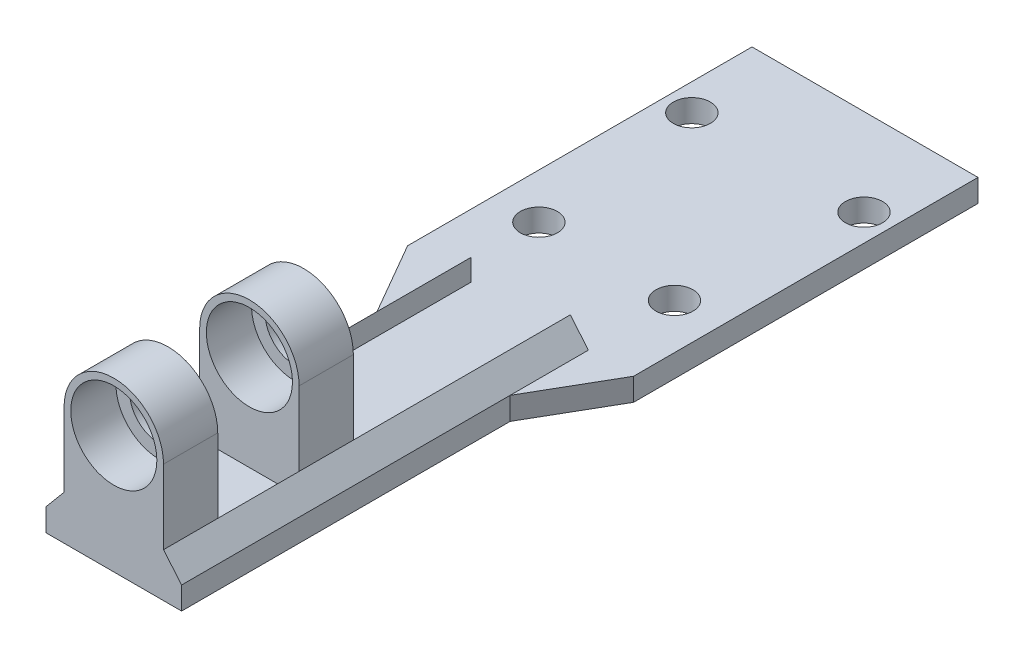
SolidWorks part; units mm, degrees
ref_plane "Plan de face" through (0, 0, 0) normal (0, 0, 1) x (1, 0, 0)
ref_plane "Plan de dessus" through (0, 0, 0) normal (0, 1, 0) x (1, 0, 0)
ref_plane "Plan de droite" through (0, 0, 0) normal (1, 0, 0) x (0, 0, -1)
sketch "Esquisse20" plane through (0, 0, 0) normal (0, -1, 0) x (1, 0, 0)
  line L0 (-25, 0) -> (-15, 17.3205)
  line L1 (-15, 17.3205) -> (-15, 90)
  line L2 (-15, 90) -> (15, 90)
  line L3 (15, 90) -> (15, 17.3205)
  line L4 (15, 17.3205) -> (25, 0)
  line L5 (0, 25.5) -> (0, 57.1166) construction
  line L6 (55, 0) -> (-55, 0) construction
  line L7 (0, -55) -> (0, 55) construction
  line L10 (-25, 0) -> (25, 0)
  dimension "D1" = 90
  dimension "D2" = 60
  dimension "D3" = 30
  dimension "D4" = 50
extrude "Boss.-Extru.7" add sketch "Esquisse20" against normal blind 5
sketch "Esquisse21" plane through (0, 0, 90) normal (0, 0, 1) x (1, 0, 0)
  line L0 (-15, 5) -> (-11, 9.767)
  line L1 (-11, 9.767) -> (-11, 26.15)
  line L2 (15, 5) -> (-15, 5)
  line L3 (11, 26.15) -> (11, 9.767)
  line L4 (11, 9.767) -> (15, 5)
  line L5 (0, 0) -> (0, 46.5044) construction
  line L7 (15, 5) -> (-15, 5) construction
  arc A0 (11, 26.15) -> (-11, 26.15) centre (0, 26.15) ccw
  point P11 (0, 5)
  dimension "D2" = 11
  dimension "D1" = 21.15
  dimension "D3" = 50
extrude "Boss.-Extru.8" add sketch "Esquisse21" against normal blind 12
ref_axis "Axe1" through (0, 5, 78) along (0, 0, -1)
sketch "Esquisse25" plane through (0, 0, 90) normal (0, 0, 1) x (1, 0, 0)
  circle A0 centre (0, 26.15) radius 9.525
  dimension "D1" = 19.05
extrude "Enlèv. mat.-Extru.1" cut sketch "Esquisse25" against normal blind 10
pattern_linear "Répétition linéaire2" count 2 spacing 30 along (0, 0, -1) of "Boss.-Extru.8", "Enlèv. mat.-Extru.1"
sketch "Esquisse22" plane through (0, 5, 0) normal (0, 1, 0) x (1, 0, 0)
  line L0 (-25, 0) -> (25, 0) construction
  line L1 (-25, 0) -> (25, 0)
  line L2 (-25, 0) -> (-25, 38.1)
  line L3 (-25, 38.1) -> (25, 38.1) construction
  line L4 (25, 0) -> (25, 38.1)
  line L5 (-15, -17.3205) -> (-25, 0) construction
  line L6 (-15, 19.05) -> (15, 19.05) construction
  line L7 (0, 38.1) -> (0, 0) construction
  line L8 (-25, 38.1) -> (-25, 76.2)
  line L9 (-25, 76.2) -> (25, 76.2)
  line L10 (25, 76.2) -> (25, 38.1)
  line L11 (-19.05, 56.9341) -> (19.05, 56.9341) construction
  line L12 (0, -20.4325) -> (0, 20.4325) construction
  circle A0 centre (-15, 19.05) radius 4.1
  circle A1 centre (15, 19.05) radius 4.1
  circle A2 centre (19.05, 56.9341) radius 4.1
  circle A3 centre (-19.05, 56.9341) radius 4.1
  point P17 (-15, 57.15)
  point P18 (0, 56.9341)
  point P25 (18.763, 50.3747)
  dimension "D3" = 8.2
  dimension "D1" = 38.1
  dimension "D2" = 10
  dimension "D4" = 38.1
  dimension "D6" = 38.1
  dimension "D5" = 38.1
extrude "Boss.-Extru.9" add sketch "Esquisse22" against normal up to surface (5 mm away) up to face at (0, 0, 35.7735)
sketch "Esquisse26" plane through (0, 0, 80) normal (0, 0, 1) x (1, 0, 0)
  circle A0 centre (0, 26.15) radius 6.5
  dimension "D1" = 13
extrude "Enlèv. mat.-Extru.2" cut sketch "Esquisse26" against normal through all
sketch "Esquisse27" plane through (0, 0, 90) normal (0, 0, 1) x (1, 0, 0)
  line L0 (-25, 5) -> (25, 5) construction
  line L1 (25, 5) -> (15, 5) construction
  line L6 (-11, 9.767) -> (-11, 5)
  line L11 (-11, 5) -> (-15, 5)
  line L13 (-11, 9.767) -> (-15, 5) construction
  line L14 (-11, 9.767) -> (-15, 5)
  line L15 (15, 5) -> (11, 9.767)
  line L16 (11, 9.767) -> (11, 5)
  line L17 (11, 5) -> (15, 5)
extrude "Boss.-Extru.10" add sketch "Esquisse27" against normal up to surface (90 mm away) up to plane "Plan de face"
